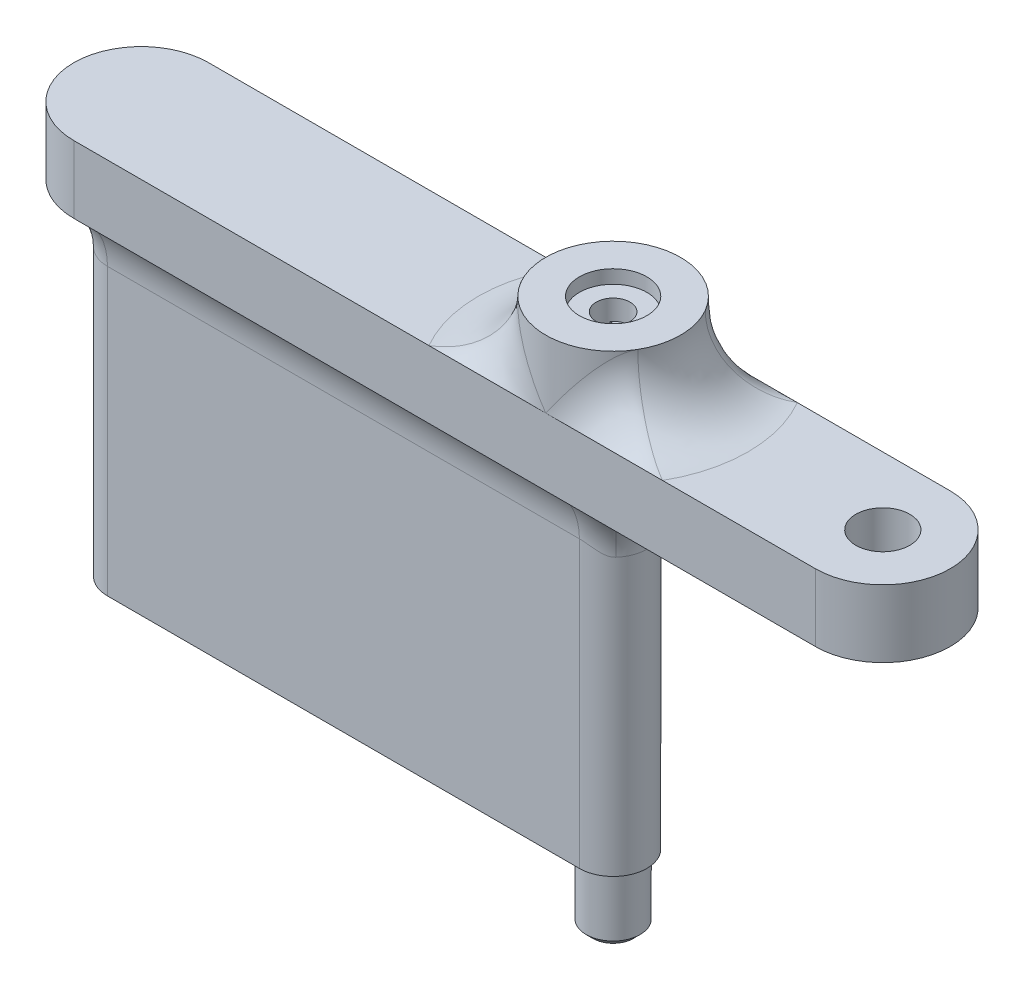
SolidWorks part; units mm, degrees
ref_plane "Front Plane" through (0, 0, 0) normal (0, 0, 1) x (1, 0, 0)
ref_plane "Top Plane" through (0, 0, 0) normal (0, 1, 0) x (1, 0, 0)
ref_plane "Right Plane" through (0, 0, 0) normal (1, 0, 0) x (0, 0, -1)
sketch "Sketch1" plane through (0, 0, 0) normal (0, 1, 0) x (1, 0, 0)
  line L0 (0, 0) -> (-70, 0) construction
  line L1 (0, -5) -> (-70, -5)
  line L2 (0, 5) -> (-70, 5)
  arc A0 (0, -5) -> (0, 5) centre (0, 0) ccw
  arc A1 (-70, 5) -> (-70, -5) centre (-70, 0) ccw
  point P3 (-35, 0)
  dimension "D1" = 70
  dimension "D2" = 10
extrude "Boss-Extrude1" add sketch "Sketch1" against normal blind 51
sketch "Sketch2" plane through (0, 0, 0) normal (0, 1, 0) x (1, 0, 0)
  line L0 (0, 0) -> (-70, 0) construction
  line L5 (0, -10) -> (-70, -10)
  line L6 (0, 10) -> (-70, 10)
  line L7 (0, 0) -> (40, 0) construction
  line L8 (0, 10) -> (40, 10)
  line L9 (0, -10) -> (40, -10)
  arc A5 (-70, 10) -> (-70, -10) centre (-70, 0) ccw
  arc A7 (40, -10) -> (40, 10) centre (40, 0) ccw
  circle A8 centre (40, 0) radius 4
  point P9 (0, 0)
  point P12 (0, 0)
  dimension "D5" = 8
  dimension "D7" = 10
  dimension "D1" = 70
  dimension "D2" = 20
  dimension "D3" = 20
  dimension "D4" = 40
  dimension "D6" = 70
extrude "Boss-Extrude2" add sketch "Sketch2" along normal blind 10
fillet "Fillet1" radius 10 1 edges at (5, 0, 0)
sketch "Sketch3" plane through (0, 10, 0) normal (0, 1, 0) x (1, 0, 0)
  circle A0 centre (0, 0) radius 10
  dimension "D1" = 20
extrude "Boss-Extrude3" add sketch "Sketch3" along normal blind 10
fillet "Fillet2" radius 10 2 edges at (10, 10, 0) (-10, 10, 0)
sketch "Sketch4" plane through (0, 20, 0) normal (0, 1, 0) x (1, 0, 0)
  circle A0 centre (0, 0) radius 5
  dimension "D1" = 10
extrude "Cut-Extrude1" cut sketch "Sketch4" against normal blind 2
sketch "Sketch5" plane through (0, 18, 0) normal (0, 1, 0) x (1, 0, 0)
  circle A0 centre (0, 0) radius 2.5
  dimension "D1" = 5
extrude "Cut-Extrude2" cut sketch "Sketch5" against normal blind 3
sketch "Sketch6" plane through (0, 15, 0) normal (0, 1, 0) x (1, 0, 0)
  line L1 (-2, -1.5) -> (2, -1.5)
  line L3 (-2, 1.5) -> (2, 1.5)
  line L5 (-2, -1.5) -> (2, 1.5) construction
  line L6 (-2, 1.5) -> (2, -1.5) construction
  circle A0 centre (0, 0) radius 2.5 construction
  arc A1 (-2, 1.5) -> (-2, -1.5) centre (0, 0) ccw
  arc A2 (2, 1.5) -> (2, -1.5) centre (0, 0) cw
  point P0 (0, 0)
  dimension "D1" = 3
extrude "Cut-Extrude3" cut sketch "Sketch6" against normal blind 7
sketch "Sketch7" plane through (0, -51, 0) normal (0, -1, 0) x (1, 0, 0)
  circle A0 centre (0, 0) radius 4
  dimension "D1" = 8
extrude "Boss-Extrude4" add sketch "Sketch7" along normal blind 10
chamfer "Chamfer1" distance 1 angle 45 1 edges at (0, -61, -4)
